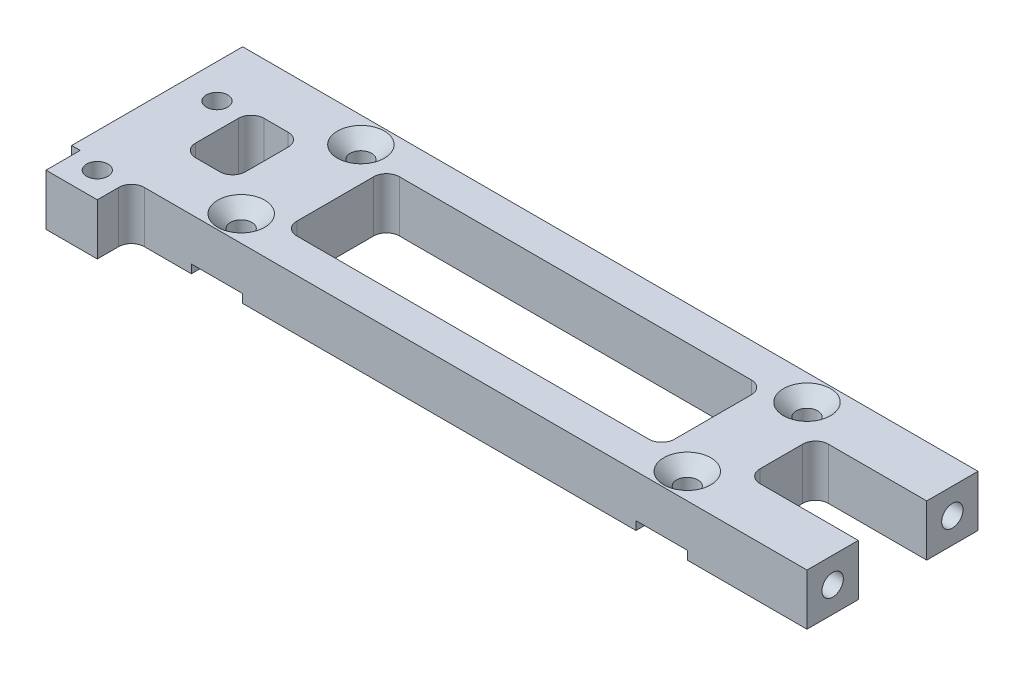
SolidWorks part; units mm, degrees
material "1060 Alloy"
ref_plane "Front Plane" through (0, 0, 0) normal (0, 0, 1) x (1, 0, 0)
ref_plane "Top Plane" through (0, 0, 0) normal (0, 1, 0) x (1, 0, 0)
ref_plane "Right Plane" through (0, 0, 0) normal (1, 0, 0) x (0, 0, -1)
sketch "Sketch2" plane through (0, 0, 0) normal (0, 1, 0) x (1, 0, 0)
  line L1 (86, -20) -> (0, -20)
  line L5 (0, -20) -> (0, 0)
  line L6 (86, -20) -> (86, 0)
  line L11 (86, 0) -> (0, 0)
  dimension "D2" = 86
  dimension "D9" = 20
extrude "Boss-Extrude1" add sketch "Sketch2" along normal blind 6
hole_wizard "Tap Drill for M3 Tap2" positions "Sketch6" profile "Sketch5" hole size "M3" standard "ISO"
sketch "Sketch6" plane through (86, 0.7792, 7.6405) normal (1, 0, 0) x (0, 0, -1)
  line L4 (-12.3595, -0.7792) -> (7.6405, -0.7792) construction
  line L6 (-12.3595, 5.2208) -> (-12.3595, -0.7792) construction
  line L7 (7.6405, 5.2208) -> (7.6405, -0.7792) construction
  point P0 (-9.3595, 2.2208)
  point P2 (4.6405, 2.2208)
  dimension "D1" = 3
  dimension "D2" = 3
  dimension "D3" = 3
sketch "Sketch5" plane through (86, 3, 17) normal (0, 1, 0) x (0, 0, -1)
  line L0 (0, 0) -> (0, 8.7511)
  line L1 (0, 8.7511) -> (1.25, 8)
  line L2 (1.25, 8) -> (1.25, 0)
  line L5 (1.25, 0) -> (0, 0)
  line L10 (0, 8.7511) -> (-1.25, 8) construction
  line L11 (0, -6.35) -> (0, 107.95) construction
  dimension "Hole Dia." = 2.5
  dimension "Hole Depth" = 8
  dimension "Drill Angle" = 118
hole_wizard "Tap Drill for M3 Tap1" positions "Sketch4" profile "Sketch3" hole size "M3" standard "ISO"
sketch "Sketch4" plane through (0, 0, 0) normal (-1, 0, 0) x (0, 0, 1)
  line L0 (0, 0) -> (20, 0) construction
  line L2 (0, 6) -> (0, 0) construction
  line L3 (20, 6) -> (20, 0) construction
  point P0 (3, 3)
  point P2 (17, 3)
  dimension "D1" = 3
  dimension "D2" = 3
  dimension "D3" = 3
sketch "Sketch3" plane through (0, 3, 3) normal (0, 1, 0) x (0, 0, 1)
  line L0 (0, 0) -> (0, 8.7511)
  line L1 (0, 8.7511) -> (1.25, 8)
  line L2 (1.25, 8) -> (1.25, 0)
  line L5 (1.25, 0) -> (0, 0)
  line L10 (0, 8.7511) -> (-1.25, 8) construction
  line L11 (0, -6.35) -> (0, 107.95) construction
  dimension "Hole Dia." = 2.5
  dimension "Hole Depth" = 8
  dimension "Drill Angle" = 118
sketch "Sketch7" plane through (0, 0, 0) normal (0, -1, 0) x (1, 0, 0)
  line L0 (0, 20) -> (86, 20) construction
  line L1 (14, 20) -> (20, 20)
  line L2 (14, 20) -> (14, 0)
  line L3 (14, 0) -> (20, 0)
  line L4 (20, 20) -> (20, 0)
  line L5 (86, 0) -> (0, 0) construction
  line L6 (0, 0) -> (0, 20) construction
  line L7 (72, 20) -> (66, 20)
  line L8 (72, 20) -> (72, 0)
  line L9 (72, 0) -> (66, 0)
  line L10 (66, 20) -> (66, 0)
  line L11 (86, 20) -> (86, 0) construction
  dimension "D1" = 14
  dimension "D2" = 6
  dimension "D3" = 14
extrude "Cut-Extrude1" cut sketch "Sketch7" against normal blind 1
hole_wizard "Tap Drill for M3x0.5 Tap1" positions "3DSketch1" profile "Sketch8" hole size "M3x0.5" standard "ANSI Metric" end condition up to next
sketch3d "3DSketch1"
  line L0 (72, 1, 0) -> (72, 1, 20) construction
  line L1 (66, 1, 0) -> (72, 1, 0) construction
  line L2 (20, 1, 20) -> (14, 1, 20) construction
  line L3 (14, 0, 20) -> (14, 0, 0) construction
  point P0 (16.8284, 1, 17)
  point P2 (16.8284, 1, 3)
  point P4 (69, 1, 17)
  point P6 (69, 1, 3)
  dimension "D1" = 3
  dimension "D2" = 3
  dimension "D3" = 3
  dimension "D4" = 3
sketch "Sketch8" plane through (16.8284, 1, 17) normal (1, 0, 0) x (0, 0, -1)
  line L0 (0, 0) -> (0, 5)
  line L1 (0, 5) -> (1.25, 5)
  line L2 (1.25, 5) -> (1.25, 0)
  line L5 (1.25, 0) -> (0, 0)
  line L11 (0, -6.35) -> (0, 107.95) construction
  dimension "Thru Hole Dia." = 2.5
  dimension "Thru Hole Depth" = 5
chamfer "Chamfer1" distance 1.5 angle 45 4 edges at (16.8284, 6, 15.75) (16.8284, 6, 1.75) (69, 6, 15.75) (69, 6, 1.75)
sketch "Sketch9" plane through (0, 6, 0) normal (0, 1, 0) x (1, 0, 0)
  line L0 (86, 0) -> (0, 0) construction
  line L1 (20.8284, -4) -> (65, -4)
  line L2 (20.8284, -4) -> (20.8284, -16)
  line L3 (20.8284, -16) -> (65, -16)
  line L4 (65, -4) -> (65, -16)
  line L5 (0, -20) -> (86, -20) construction
  line L7 (7, -6) -> (12.8284, -6)
  line L8 (7, -6) -> (7, -14)
  line L9 (7, -14) -> (12.8284, -14)
  line L10 (12.8284, -6) -> (12.8284, -14)
  line L11 (86, -20) -> (86, 0) construction
  line L12 (86, -6) -> (73, -6)
  line L13 (86, -6) -> (86, -14)
  line L14 (86, -14) -> (73, -14)
  line L15 (73, -6) -> (73, -14)
  line L16 (0, 0) -> (0, -20) construction
  circle A0 centre (16.8284, -17) radius 1.25 construction
  circle A1 centre (69, -3) radius 1.25 construction
  circle A2 centre (16.8284, -3) radius 1.25 construction
  dimension "D1" = 4
  dimension "D2" = 4
  dimension "D5" = 4
  dimension "D8" = 4
  dimension "D3" = 4
  dimension "D4" = 4
  dimension "D6" = 6
  dimension "D7" = 6
  dimension "D9" = 6
  dimension "D10" = 6
  dimension "D11" = 7
extrude "Cut-Extrude2" cut sketch "Sketch9" against normal up to next
sketch "Sketch10" plane through (0, 6, 0) normal (0, 1, 0) x (1, 0, 0)
  line L0 (7, -6) -> (7, -14) construction
  line L1 (1, -20) -> (7, -20)
  line L2 (1, -20) -> (1, -24)
  line L3 (1, -24) -> (7, -24)
  line L4 (7, -20) -> (7, -24)
  line L5 (0, -20) -> (86, -20) construction
  line L6 (0, 0) -> (0, -20) construction
  dimension "D1" = 4
  dimension "D2" = 1
extrude "Boss-Extrude2" add sketch "Sketch10" against normal up to surface (6 mm away) up to face at (9.9142, 0, 10)
fillet "Fillet1" radius 1.5 11 edges at (73, 3, 14) (73, 3, 6) (20.8284, 3, 16) (20.8284, 3, 4) (65, 3, 16) (65, 3, 4) (12.8284, 3, 14) (12.8284, 3, 6) (7, 3, 14) (7, 3, 6)
hole_wizard "Tap Drill for M3 Tap3" positions "Sketch12" profile "Sketch11" hole size "M3" standard "ISO" end condition up to next
sketch "Sketch12" plane through (0, 6, 0) normal (0, 1, 0) x (1, 0, 0)
  line L0 (86, 0) -> (0, 0) construction
  line L1 (8.5, -14) -> (11.3284, -14) construction
  line L4 (0, 0) -> (0, -20) construction
  point P0 (4, -7)
  point P2 (4, -21)
  dimension "D1" = 7
  dimension "D2" = 7
  dimension "D3" = 4
sketch "Sketch11" plane through (4, 6, 7) normal (1, 0, 0) x (0, 0, 1)
  line L0 (0, 0) -> (0, 6)
  line L1 (0, 6) -> (1.25, 6)
  line L2 (1.25, 6) -> (1.25, 0)
  line L5 (1.25, 0) -> (0, 0)
  line L11 (0, -6.35) -> (0, 107.95) construction
  dimension "Thru Hole Dia." = 2.5
  dimension "Thru Hole Depth" = 6
